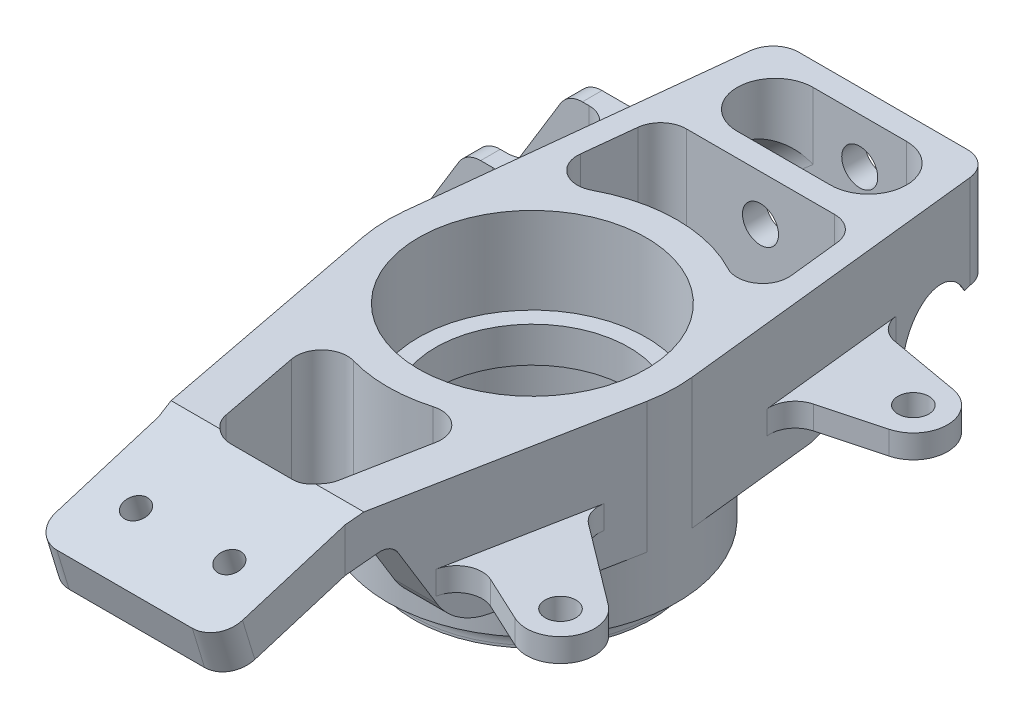
SolidWorks part; units mm, degrees
material "6061-T6 (SS)"
ref_plane "Front Plane" through (0, 0, 0) normal (0, 0, 1) x (1, 0, 0)
ref_plane "Top Plane" through (0, 0, 0) normal (0, 1, 0) x (1, 0, 0)
ref_plane "Right Plane" through (0, 0, 0) normal (1, 0, 0) x (0, 0, -1)
sketch "UBJ LBJ Geometry" plane through (0, 0, 0) normal (1, 0, 0) x (0, 0, -1)
  line L0 (0, 0) -> (0, -97.4059) construction
  line L1 (0, 0) -> (-30.7529, 0) construction
  line L2 (0, 22) -> (-45.5659, 22) construction
  line L3 (0, -10.5425) -> (-23.1063, -10.5425) construction
  line L4 (-84.7344, -51.66) -> (78.74, -22.958) construction
  line L5 (49.4563, 0) -> (49.4563, -88.2735) construction
  circle A0 centre (-84.7344, -51.66) radius 10.3251 construction
  circle A1 centre (78.74, -22.958) radius 10.3251 construction
  dimension "D7" = 20.6502
  dimension "D8" = 20.6502
  dimension "D1" = 22
  dimension "D2" = 32.5425
  dimension "D3" = 44.958
  dimension "D4" = 73.66
  dimension "D5" = 84.7344
  dimension "D6" = 78.74
  dimension "D9" = 29.2837
ref_plane "Wheel Face " through (0, 22, 0) normal (0, -1, 0) x (-1, 0, 0)
ref_plane "Upright Face" through (0, -10.5425, 0) normal (0, -1, 0) x (-1, 0, 0)
ref_plane "Tie Bracket Plane" through (0, 0, -49.4563) normal (0, 0, 1) x (1, 0, 0)
sketch "Tie Bracket Geometry" plane through (0, 0, -49.4563) normal (0, 0, 1) x (1, 0, 0)
  line L0 (0, -28.0995) -> (-60.5599, -51.7108) construction
  line L4 (0, 200000) -> (0, -200097.4059) construction
  circle A0 centre (-60.5599, -51.7108) radius 8.948 construction
  dimension "D1" = 65
  dimension "D2" = 68.7
sketch "Sketch1" plane through (0, 0, 0) normal (0, 0, 1) x (1, 0, 0)
  line L1 (-75.0953, -10.5425) -> (75.0953, -10.5425) construction
  line L2 (-39.37, -10.5425) -> (-39.37, -61.3425)
  line L3 (-39.37, -61.3425) -> (-32.258, -61.3425)
  line L4 (-32.258, -61.3425) -> (-32.258, -68.9625)
  line L5 (-32.258, -68.9625) -> (-30.9829, -68.9625)
  line L8 (-30.9829, -10.5425) -> (-30.9829, -34.0375)
  line L9 (-30.9829, -34.0375) -> (-26.289, -34.0375)
  line L10 (-26.289, -34.0375) -> (-26.289, -43.6895)
  line L11 (-26.289, -43.6895) -> (-30.9829, -43.6895)
  line L12 (-30.9829, -43.6895) -> (-30.9829, -68.9625)
  line L15 (-39.37, -10.5425) -> (-30.9829, -10.5425)
  line L17 (0, 0) -> (0, -23.5057) construction
  dimension "D1" = 9.652
  dimension "D2" = 61.9658
  dimension "D3" = 25.273
  dimension "D4" = 52.578
  dimension "D5" = 23.495
  dimension "D6" = 50.8
  dimension "D7" = 78.74
  dimension "D8" = 64.516
revolve "Bearing Housing Revolve" add sketch "Sketch1" angle 360 about L17
fillet "Bearing Housing Fillet" radius 6.985 1 edges at (0, -61.3425, 32.258)
sketch "Sketch2" plane through (0, -10.5425, 0) normal (0, -1, 0) x (-1, 0, 0)
  line L3 (39.37, -43.18) -> (39.37, 0)
  line L4 (-39.37, -43.18) -> (-39.37, 0)
  line L5 (39.37, -43.18) -> (-39.37, -43.18)
  circle A4 centre (0, 0) radius 39.37 construction
  arc A5 (39.37, 0) -> (-39.37, 0) centre (0, 0) cw
  dimension "D1" = 43.18
extrude "UBJ Prep" add sketch "Sketch2" along normal blind 35.56
sketch "Sketch3" plane through (-39.37, 0, 0) normal (-1, 0, 0) x (0, 0, 1)
  line L0 (-120.7672, 22) -> (120.7672, 22) construction
  line L1 (43.18, -10.5425) -> (72.0727, -10.5425)
  line L2 (72.0727, -10.5425) -> (110.937, -22.4245)
  line L3 (110.937, -22.4245) -> (107.5952, -33.355)
  line L4 (107.5952, -33.355) -> (68.7309, -21.473)
  line L6 (43.18, -46.1025) -> (43.18, -10.5425)
  line L7 (72.0727, -10.5425) -> (68.7309, -21.473) construction
  line L8 (104.3241, 12.415) -> (84.7344, -51.66) construction
  line L9 (55.3259, -39.0344) -> (64.3045, -23.2342)
  circle A0 centre (84.7344, -51.66) radius 12.7 construction
  arc A1 (43.18, -46.1025) -> (55.3259, -39.0344) centre (43.18, -32.1325) ccw
  arc A2 (68.7309, -21.473) -> (64.3045, -23.2342) centre (67.617, -25.1166) ccw
  dimension "D7" = 7.62
  dimension "D8" = 27.94
  dimension "D9" = 25.4
  dimension "D1" = 73.66
  dimension "D2" = 84.7344
  dimension "D3" = 11.43
  dimension "D4" = 40.64
  dimension "D5" = 17
  dimension "D6" = 16.51
extrude "UBJ Extrude " add sketch "Sketch3" against normal up to surface (78.74 mm away) up to face at (39.37, -28.3225, 21.59)
sketch "Sketch4" plane through (0, -0.4206, -0.1286) normal (0, -0.9563, -0.2924) x (1, 0, 0)
  line L0 (0, 112.6458) -> (0, 27.8969) construction
  line L1 (39.37, 112.6458) -> (-39.37, 112.6458) construction
  line L3 (-12.7, 96.1358) -> (12.7, 96.1358) construction
  circle A0 centre (-12.7, 96.1358) radius 3.2639
  circle A1 centre (12.7, 96.1358) radius 3.2639
  point P8 (0, 96.1358)
  dimension "D2" = 6.5278
  dimension "D1" = 25.4
extrude "Camber Block Holes" cut sketch "Sketch4" against normal up to surface (11.43 mm away) up to face at (0, -16.4835, 91.5049)
sketch "Sketch5" plane through (0, -46.1025, 0) normal (0, -1, 0) x (1, 0, 0)
  line L0 (-25.4, 107.5952) -> (-25.4, 76.3532)
  line L1 (25.4, 110.937) -> (39.37, 110.937)
  line L2 (39.37, 107.5952) -> (-39.37, 107.5952) construction
  line L4 (-25.4, 76.3532) -> (-38.6608, 7.4393)
  line L5 (25.4, 107.5952) -> (25.4, 76.3532)
  line L6 (25.4, 76.3532) -> (38.6608, 7.4393)
  line L7 (-25.4, 107.5952) -> (-25.4, 110.937)
  line L8 (39.37, 110.937) -> (-39.37, 110.937) construction
  line L9 (25.4, 107.5952) -> (25.4, 110.937)
  line L10 (-25.4, 110.937) -> (-39.37, 110.937)
  line L11 (-39.37, 110.937) -> (-39.37, 0)
  line L12 (39.37, 110.937) -> (39.37, 0)
  line L13 (-14.2785, 73.66) -> (14.2785, 73.66)
  line L14 (-14.2785, 73.66) -> (-22.1955, 32.517)
  line L15 (14.2785, 73.66) -> (22.1955, 32.517)
  arc A0 (-39.37, 0) -> (-38.6608, 7.4393) centre (0, 0) cw
  circle A1 centre (0, 0) radius 39.37 construction
  arc A2 (39.37, 0) -> (-39.37, 0) centre (0, 0) ccw construction
  arc A3 (39.37, 0) -> (38.6608, 7.4393) centre (0, 0) ccw
  arc A4 (-22.1955, 32.517) -> (22.1955, 32.517) centre (0, 0) cw
  point P31 (0, 73.66)
  dimension "D1" = 25.4
  dimension "D2" = 11.43
  dimension "D3" = 31.242
  dimension "D4" = 73.66
extrude "Weight Saving" cut sketch "Sketch5" against normal through all
fillet "Fillet2" radius 6.985 4 edges at (22.1955, -28.3225, 32.517) (-22.1955, -28.3225, 32.517) (14.2785, -17.0039, 73.66) (-14.2785, -17.0039, 73.66)
sketch "Sketch6" plane through (0, -10.5425, 0) normal (0, -1, 0) x (-1, 0, 0)
  line L0 (-39.37, 0) -> (-39.37, 40.64)
  line L1 (-39.37, 40.64) -> (39.37, 40.64)
  line L2 (39.37, 40.64) -> (39.37, 0)
  circle A0 centre (0, 0) radius 39.37 construction
  arc A1 (-39.37, 0) -> (39.37, 0) centre (0, 0) cw
  dimension "D1" = 40.64
extrude "LBJ Prep" add sketch "Sketch6" along normal blind 35.56
sketch "Sketch8" plane through (-39.37, 0, 0) normal (-1, 0, 0) x (0, 0, 1)
  line L0 (-40.64, -10.5425) -> (-95.4151, -10.5425)
  line L1 (-95.4151, -10.5425) -> (-95.4151, -35.9425)
  line L2 (-95.4151, -35.9425) -> (-89.0651, -35.9425)
  line L7 (-40.64, -46.1025) -> (-40.64, -10.5425)
  line L8 (-120.7672, 22) -> (120.7672, 22) construction
  line L9 (-89.0651, -35.9425) -> (-89.0651, -10.5425) construction
  line L10 (-89.0651, -35.9425) -> (-40.64, -46.1025)
  circle A0 centre (-78.74, -22.958) radius 10.3251 construction
  dimension "D3" = 20.6502
  dimension "D1" = 78.74
  dimension "D2" = 44.958
  dimension "D4" = 6.35
  dimension "D5" = 25.4
extrude "LBJ Area " add sketch "Sketch8" against normal up to surface (78.74 mm away) up to face at (39.37, -28.3225, -20.32)
sketch "Sketch7" plane through (0, -46.1025, 0) normal (0, -1, 0) x (1, 0, 0)
  line L0 (-12.7, -78.74) -> (12.7, -78.74) construction
  line L1 (0, -200000) -> (0, 200045.5659) construction
  line L2 (-12.7, -68.4149) -> (12.7, -68.4149)
  line L3 (-12.7, -89.0651) -> (12.7, -89.0651)
  line L4 (-29.21, -95.4151) -> (-39.1385, -4.2631)
  line L5 (39.37, -95.4151) -> (-39.37, -95.4151) construction
  line L6 (29.21, -95.4151) -> (39.1385, -4.2631)
  line L7 (-29.21, -95.4151) -> (-39.37, -95.4151)
  line L8 (-39.37, -95.4151) -> (-39.37, 0)
  line L9 (29.21, -95.4151) -> (39.37, -95.4151)
  line L10 (39.37, -95.4151) -> (39.37, 0)
  line L13 (-26.455, -62.0649) -> (26.455, -62.0649)
  line L14 (26.455, -62.0649) -> (30.5043, -24.8895)
  line L15 (-26.455, -62.0649) -> (-30.5043, -24.8895)
  arc A0 (-12.7, -68.4149) -> (-12.7, -89.0651) centre (-12.7, -78.74) ccw
  arc A1 (12.7, -89.0651) -> (12.7, -68.4149) centre (12.7, -78.74) ccw
  circle A2 centre (0, 0) radius 39.37 construction
  arc A3 (-39.37, 0) -> (39.37, 0) centre (0, 0) ccw construction
  arc A4 (39.37, 0) -> (39.1385, -4.2631) centre (0, 0) cw
  arc A5 (-39.37, 0) -> (-39.1385, -4.2631) centre (0, 0) ccw
  arc A6 (-30.5043, -24.8895) -> (30.5043, -24.8895) centre (0, 0) ccw
  point P4 (0, -78.74)
  point P28 (0, -62.0649)
  dimension "D1" = 78.74
  dimension "D2" = 20.6502
  dimension "D3" = 25.4
  dimension "D4" = 10.16
  dimension "D5" = 6.35
  dimension "D6" = 6.35
extrude "LBJ Taper And Slot" cut sketch "Sketch7" against normal up to surface (35.56 mm away) up to face at (0, -10.5425, 30.9829)
fillet "Fillet3" radius 6.985 4 edges at (26.455, -26.0749, -62.0649) (-26.455, -26.0749, -62.0649) (30.5043, -28.3225, -24.8895) (-30.5043, -28.3225, -24.8895)
extrude "LBJ Holes 3/8 Close Fit Hole" cut sketch "Sketch9" against normal up to surface (33.3502 mm away) up to face at (0, -26.0749, -62.0649)
sketch "Sketch9" plane through (0, 0, -95.4151) normal (0, 0, -1) x (-1, 0, 0)
  circle A0 centre (0, -22.958) radius 4.9022
  dimension "D2" = 9.8044
  dimension "D1" = 22.958
ref_plane "Brake Mounting Plane" through (0, -30.7025, 0) normal (0, 1, 0) x (1, 0, 0)
sketch "Sketch10" plane through (0, -30.7025, 0) normal (0, 1, 0) x (1, 0, 0)
  line L0 (87.9814, 0) -> (161.3053, 0) construction
  line L1 (0, 72.9505) -> (0, 47.1638) construction
  line L2 (55.6514, 48) -> (55.6514, -48) construction
  line L3 (58.0532, 39.0362) -> (35.9947, 33.1256)
  line L4 (39.1385, 4.2631) -> (29.21, 95.4151) construction
  line L5 (35.9947, 33.1256) -> (32.9114, 61.4328)
  line L6 (32.9114, 61.4328) -> (57.2629, 57.139)
  line L7 (61.2362, -40.5887) -> (35.9487, -21.5332)
  line L8 (26.2237, -72.0727) -> (38.6608, -7.4393) construction
  line L9 (35.9487, -21.5332) -> (31.0895, -46.7859)
  line L10 (31.0895, -46.7859) -> (51.7295, -56.4105)
  circle A0 centre (55.6514, 48) radius 4.2
  circle A1 centre (55.6514, -48) radius 4.2
  arc A2 (51.7295, -56.4105) -> (61.2362, -40.5887) centre (55.6514, -48) ccw
  arc A3 (58.0532, 39.0362) -> (57.2629, 57.139) centre (55.6514, 48) ccw
  point P7 (55.6514, 0)
  dimension "D2" = 8.4
  dimension "D3" = 5.08
  dimension "D4" = 5.08
  dimension "D1" = 96
  dimension "D5" = 55.6514
  dimension "D6" = 80
  dimension "D7" = 75
  dimension "D8" = 53
  dimension "D9" = 65
extrude "Brake Mounts" add sketch "Sketch10" against normal blind 6.35
fillet "Fillet4" radius 6.985 4 edges at (35.9487, -33.8775, 21.5332) (31.0895, -33.8775, 46.7859) (35.9947, -33.8775, -33.1256) (32.9114, -33.8775, -61.4328)
sketch "Sketch17" plane through (0, -37.0525, 0) normal (0, -1, 0) x (1, 0, 0)
  line L1 (36.7718, 17.2561) -> (29.3968, 55.5823) construction
  line L3 (32.3437, -66.6449) -> (36.6432, -27.1723) construction
  line L6 (57.2629, -57.139) -> (38.0747, -60.5224) construction
  line L12 (61.2362, 40.5887) -> (39.4272, 24.1544) construction
  circle A0 centre (40.1051, 38.5795) radius 4.7625
  circle A1 centre (41.7973, -47.2925) radius 4.7625
  dimension "D1" = 9.525
  dimension "D2" = 9.525
  dimension "D3" = 2.54
  dimension "D4" = 2.54
  dimension "D5" = 7.62
  dimension "D6" = 6.35
extrude "rotor Cut " [suppressed] cut sketch "Sketch17" against normal up to surface (6.35 mm away) up to plane "Brake Mounting Plane"
sketch "Sketch16" plane through (0, -46.1025, 0) normal (0, 1, 0) x (1, 0, 0)
  line L0 (-38.6345, 8.89) -> (-55.7371, 8.89)
  line L1 (-38.6608, -7.4393) -> (-26.2237, -72.0727) construction
  line L2 (-55.7371, 8.89) -> (-55.7371, -8.89)
  line L3 (-55.7371, -8.89) -> (-38.3816, -8.89)
  line L5 (-29.21, 95.4151) -> (-39.1385, 4.2631) construction
  line L6 (-38.6345, 8.89) -> (-38.3816, -8.89)
  circle A0 centre (-46.609, 0) radius 5.9531
  point P8 (-55.7371, 0)
  dimension "D1" = 3.175
  dimension "D3" = 11.9062
  dimension "D2" = 46.609
  dimension "D4" = 17.78
extrude "Speed Sensor Mount" add sketch "Sketch16" along normal blind 5.08
fillet "Speed Sensor Fillet" radius 6.985 4 edges at (-55.7371, -43.5625, 8.89) (-55.7371, -43.5625, -8.89) (-38.3816, -43.5625, 8.89) (-38.6345, -43.5625, -8.89)
thread "15/32-32" pitch 0.9071 method cut profile "Thread Profile1" start angle 0, offset 1, length 10, pitch 0.7937, diameter 11.9062
ref_plane "Plane1" through (-40.6559, -45.1025, 0) normal (0, 0, 1) x (1, 0, 0)
sketch "Thread Profile1" plane through (-40.6559, -45.1025, 0) normal (0, 0, 1) x (1, 0, 0)
  line L0 (0, 0) -> (0, 0.9071) construction
  line L1 (0, 0) -> (0.491, 0.2835)
  line L2 (0.491, 0.2835) -> (0.491, 0.3969)
  line L3 (0.491, 0.3969) -> (0, 0.6804)
  line L4 (0.491, 0.3402) -> (0, 0.3402) construction
  line L11 (0, 0) -> (0, 0.6804)
  point P2 (0, 0)
  dimension "Pitch" = 0.9071
  dimension "Profile_Angle" = 60
  dimension "Profile_Land" = 0.1134
  dimension "Profile_Height" = 0.491
sketch "Sketch12" plane through (0, 0, -49.4563) normal (0, 0, 1) x (1, 0, 0)
  line L0 (0, 3.2946) -> (0, -38.5659) construction
  line L1 (-90.5661, 0) -> (-38.2005, 0) construction
  line L2 (-68.726, -10.5425) -> (-68.726, -51.7108)
  line L3 (-52.3938, -10.5425) -> (-52.3938, -51.7108)
  line L4 (-68.726, -10.5425) -> (-52.3938, -10.5425)
  line L6 (-75.0953, -10.5425) -> (75.0953, -10.5425) construction
  circle A0 centre (-60.5599, -51.7108) radius 3.2639
  arc A1 (-68.726, -51.7108) -> (-52.3938, -51.7108) centre (-60.5599, -51.7108) ccw
  dimension "D1" = 6.5278
  dimension "D2" = 4.9022
extrude "Initial Toe Bracket" add sketch "Sketch12" along normal blind 16.51 and the other way blind 16.51 separate body
sketch "Sketch13" plane through (-52.3938, 0, 0) normal (1, 0, 0) x (0, 0, -1)
  line L0 (32.9463, -16.8925) -> (65.9663, -16.8925)
  line L1 (65.9663, -51.7108) -> (65.9663, -10.5425) construction
  line L2 (65.9663, -16.8925) -> (65.9663, -38.4825)
  line L3 (32.9463, -16.8925) -> (32.9463, -38.4825)
  line L4 (200000, -10.5425) -> (-200023.1063, -10.5425) construction
  line L5 (32.9463, -38.4825) -> (65.9663, -38.4825)
  line L6 (32.9463, -51.7108) -> (32.9463, -10.5425) construction
  dimension "D1" = 6.35
  dimension "D2" = 21.59
extrude "Toe Bracket Connection to Upright" add sketch "Sketch13" along normal up to surface (19.9762 mm away) up to face at (-34.7109, -33.4025, -44.9123)
sketch "Sketch14" plane through (0, 0, -65.9663) normal (0, 0, -1) x (-1, 0, 0)
  line L0 (52.3938, -16.8925) -> (68.726, -16.8925)
  line L1 (68.726, -10.5425) -> (68.726, -51.7108) construction
  line L2 (68.726, -16.8925) -> (68.726, -10.5425)
  line L3 (68.726, -10.5425) -> (52.3938, -10.5425)
  line L4 (52.3938, -10.5425) -> (52.3938, -16.8925)
extrude "Excess Toe Bracket Cut" cut sketch "Sketch14" against normal up to surface (33.02 mm away) up to face at (-52.382, -30.4278, -32.9463)
sketch "Sketch19" plane through (0, 0, -32.9463) normal (0, 0, 1) x (1, 0, 0)
  line L1 (-43.6343, -38.4825) -> (-52.3938, -38.4825)
  line L2 (-52.3938, -38.4825) -> (-53.0672, -54.958)
  line L3 (-36.0143, -38.4825) -> (-52.3938, -38.4825) construction
  line L4 (-36.0143, -16.8925) -> (-36.0143, -38.4825) construction
  line L5 (-53.0672, -54.958) -> (-46.8388, -40.5862)
  arc A0 (-68.726, -51.7108) -> (-52.3938, -51.7108) centre (-60.5599, -51.7108) ccw construction
  arc A1 (-43.6343, -38.4825) -> (-46.8388, -40.5862) centre (-43.6343, -41.975) ccw
  dimension "D2" = 6.985
  dimension "D1" = 7.62
extrude "Adding To Toe" add sketch "Sketch19" against normal up to surface (33.02 mm away) up to face at (-51.1792, -37.0563, -65.9663)
sketch "Sketch20" plane through (0, 0, -32.9463) normal (0, 0, 1) x (1, 0, 0)
  line L0 (-50.946, -16.8925) -> (-68.726, -16.8925)
  line L1 (-36.0143, -16.8925) -> (-68.726, -16.8925) construction
  line L2 (-68.726, -16.8925) -> (-68.726, -46.1025)
  line L3 (-68.726, -16.8925) -> (-68.726, -51.7108) construction
  line L4 (-68.726, -46.1025) -> (-50.946, -16.8925)
  dimension "D1" = 17.78
  dimension "D2" = 29.21
extrude "Cut-Extrude1" cut sketch "Sketch20" against normal up to surface (33.02 mm away) up to face at (-49.6376, -37.6998, -65.9663)
sketch "Sketch15" plane through (-68.726, 0, 0) normal (-1, 0, 0) x (0, 0, 1)
  line L0 (-60.6323, -16.8925) -> (-38.2803, -16.8925)
  line L1 (-38.2803, -16.8925) -> (-38.2803, -59.8769)
  line L2 (-65.9663, -59.8769) -> (-32.9463, -59.8769) construction
  line L3 (-38.2803, -59.8769) -> (-60.6323, -59.8769)
  line L4 (-60.6323, -59.8769) -> (-60.6323, -16.8925)
  line L6 (-49.4563, -25.7825) -> (-49.4563, -39.109) construction
  line L8 (-32.9463, -16.8925) -> (-65.9663, -16.8925) construction
  point P9 (-49.4563, -16.8925)
  point P11 (-49.4563, -16.8925)
  dimension "D1" = 22.352
extrude "Toe Bracket Slot" cut sketch "Sketch15" against normal blind 30.48
fillet "Toe Bracket Fillet" radius 6.985 2 edges at (-32.4176, -27.6875, -65.9663) (-36.0143, -27.6875, -32.9463)
fillet "Fillet7" radius 6.985 4 edges at (-68.726, -46.1025, -35.6133) (-68.726, -46.1025, -63.2993) (-50.946, -16.8925, -63.2993) (-50.946, -16.8925, -35.6133)
fillet "Inside Toe Fillet" radius 6.985 2 edges at (-38.246, -27.6875, -38.2803) (-38.246, -27.6875, -60.6323)
fillet "Outside Fillets" radius 6.985 4 edges at (-25.4, -27.8897, 109.2661) (25.4, -27.8897, 109.2661) (29.21, -23.2425, -95.4151) (-29.21, -23.2425, -95.4151)
sketch "Angle Reference" plane through (0, 0, -95.4151) normal (0, 0, -1) x (-1, 0, 0)
  line L0 (0, -22.958) -> (32.5253, -73.0426) construction
  line L1 (0, 0) -> (0, -88.2735) construction
  line L2 (0, -22.958) -> (69.6053, -82.0294) construction
  dimension "D1" = 33
  dimension "D2" = 16.68
ref_plane "Plane2" through (0, -22.958, -78.74) normal (-0.7624, -0.6471, 0) x (0, 0, 1)
sketch "Sketch22" plane through (0, -22.958, -78.74) normal (-0.7624, -0.6471, 0) x (0, 0, 1)
  line L0 (0, 3.81) -> (0, -5.08) construction
  line L3 (10.3251, 3.81) -> (10.3251, -5.08)
  line L4 (-10.3251, 3.81) -> (-10.3251, -5.08)
  arc A2 (10.3251, 3.81) -> (-10.3251, 3.81) centre (0, 3.81) ccw
  arc A3 (-10.3251, -5.08) -> (10.3251, -5.08) centre (0, -5.08) ccw
  point P2 (0, -0.635)
  dimension "D1" = 20.6502
  dimension "D2" = 3.81
  dimension "D3" = 8.89
extrude "Angle Slot Cut" cut sketch "Sketch22" along normal through all
mirror "Mirror1" about plane through (0, 0, 0) normal (1, 0, 0) of "Angle Slot Cut"
equation "\"Wheel_Offset\"= 22mm"
equation "\"HUB_to_UBJ_Lat\"= 2.9in"
equation "\"Hub_to_UBJ_Vert\"= 3.336in"
equation "\"Hub_to_LBJ_Lat\"= 1.77in"
equation "\"Hub_to_LBJ_Vert\"= 3.1in"
equation "\"Wheel_face_to_Upright_back\"= 1.2812in'This is the distance between the whee face to the upright back."
equation "\"UBJ_Angle\"= 17deg"
equation "\"D2@UBJ LBJ Geometry\" = \"Wheel_face_to_Upright_back\""
equation "\"D3@UBJ LBJ Geometry\" = \"Hub_to_LBJ_Lat\""
equation "\"D4@UBJ LBJ Geometry\" = \"HUB_to_UBJ_Lat\""
equation "\"D5@UBJ LBJ Geometry\" = \"Hub_to_UBJ_Vert\""
equation "\"D6@UBJ LBJ Geometry\" = \"Hub_to_LBJ_Vert\""
equation "\"D1@Sketch3\"=\"HUB_to_UBJ_Lat\""
equation "\"D2@Sketch3\"=\"Hub_to_UBJ_Vert\""
equation "\"D1@Sketch8\"=\"Hub_to_LBJ_Vert\""
equation "\"D2@Sketch8\"=\"Hub_to_LBJ_Lat\""
equation "\"Hub_Tie_Bracket_Vert\"= 2in'(Not Given) Ask Sus and Controls later"
equation "\"Tie_Beta\"= 21.3deg'From FE11 Master "
equation "\"Toe_Arm\"= 65mm'From FE11 Master (Assume Dist start at KPI)"
equation "\"D1@Sketch7\"=\"Hub_to_LBJ_Vert\""
equation "\"D1@Sketch9\"=\"Hub_to_LBJ_Lat\"-\"Wheel_Offset\""
equation "\"D1@Tie Bracket Geometry\" = \"Toe_Arm\""
equation "\"D2@Tie Bracket Geometry\" = 90 - \"Tie_Beta\""
equation "\"oranizeBlock\"= 0"
equation "\"BrakeAngle\"= 65deg"
equation "\"D5@Sketch3\"=\"UBJ_Angle\""
equation "\"D1@Sketch7\"=\"Hub_to_LBJ_Lat\""
